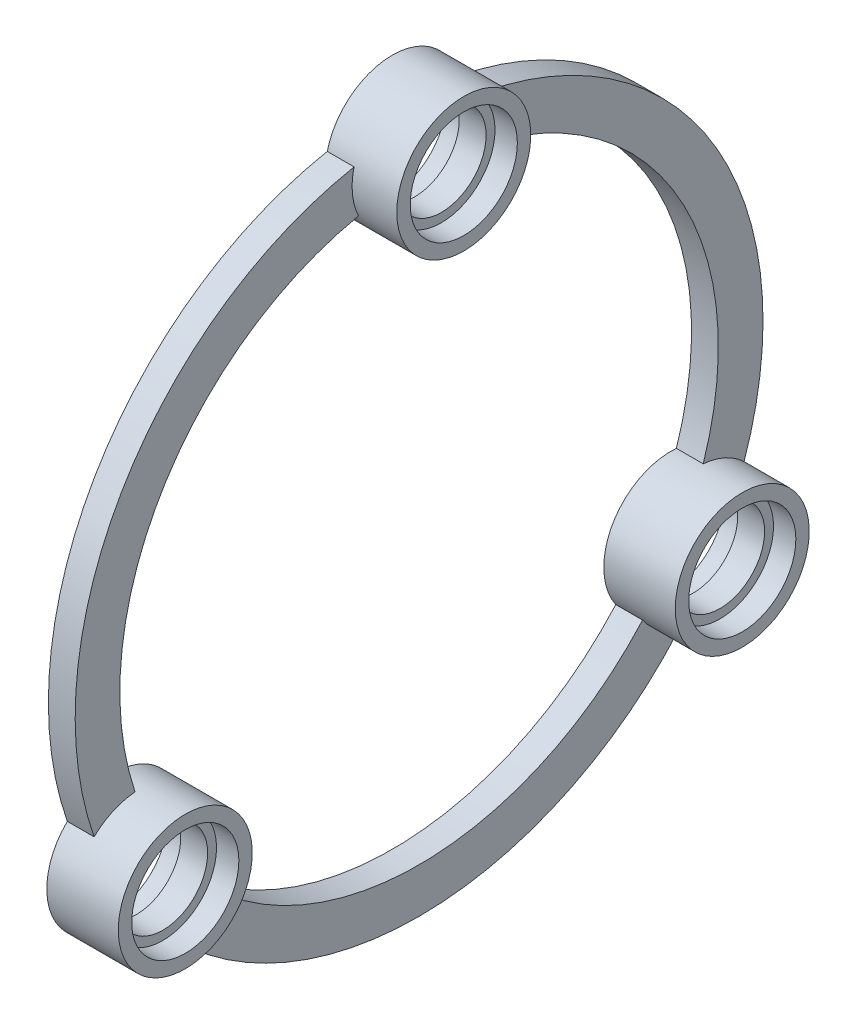
SolidWorks part; units mm, degrees
ref_plane "Спереди" through (0, 0, 0) normal (0, 0, 1) x (1, 0, 0)
ref_plane "Сверху" through (0, 0, 0) normal (0, 1, 0) x (1, 0, 0)
ref_plane "Справа" through (0, 0, 0) normal (1, 0, 0) x (0, 0, -1)
sketch "Эскиз3" plane through (0, 0, 0) normal (1, 0, 0) x (0, 0, -1)
  circle A0 centre (0, 0) radius 36 construction
  point P2 (0, 0)
  dimension "D1" = 72
sketch "Эскиз1" plane through (0, 0, 0) normal (1, 0, 0) x (0, 0, -1)
  line L0 (38.5, 0) -> (33.5, 0) construction
  circle A3 centre (0, 0) radius 38.5
  circle A4 centre (0, 0) radius 33.5
  circle A5 centre (0, 0) radius 36 construction
  point P9 (36, 0)
  dimension "D1" = 5
extrude "Бобышка-Вытянуть1" add sketch "Эскиз1" along normal blind 3
sketch "Эскиз2" plane through (0, 0, 0) normal (-1, 0, 0) x (0, 0, 1)
  circle A0 centre (0, 36) radius 7.5
  circle A1 centre (0, 0) radius 36 construction
  point P2 (0, 47.0548)
  dimension "D1" = 15
extrude "Бобышка-Вытянуть2" add sketch "Эскиз2" against normal blind 8
sketch "Эскиз4" plane through (0, 0, 0) normal (-1, 0, 0) x (0, 0, 1)
  circle A0 centre (0, 36) radius 5
  dimension "D1" = 10
extrude "Вырез-Вытянуть1" cut sketch "Эскиз4" against normal through all
sketch "Эскиз5" plane through (0, 0, 0) normal (-1, 0, 0) x (0, 0, 1)
  circle A0 centre (0, 36) radius 6
  dimension "D1" = 12
extrude "Вырез-Вытянуть2" cut sketch "Эскиз5" against normal blind 2.5
sketch "Эскиз6" plane through (8, 0, 0) normal (1, 0, 0) x (0, 0, -1)
  circle A0 centre (0, 36) radius 6
  dimension "D1" = 12
extrude "Вырез-Вытянуть3" cut sketch "Эскиз6" against normal blind 2.5
pattern_circular "Круговой массив1" count 3 over 360 about axis through (3, 0, 0) along (-1, 0, 0) of "Бобышка-Вытянуть2", "Вырез-Вытянуть1", "Вырез-Вытянуть2", "Вырез-Вытянуть3"
